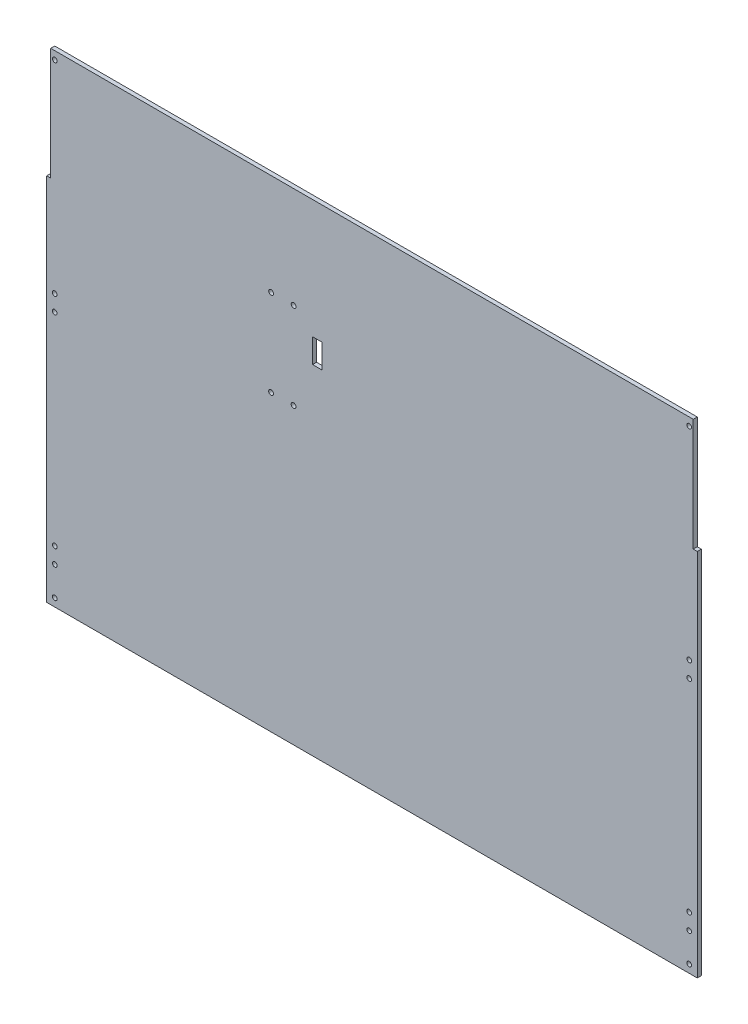
SolidWorks part; units mm, degrees
ref_plane "Front Plane" through (0, 0, 0) normal (0, 0, 1) x (1, 0, 0)
ref_plane "Top Plane" through (0, 0, 0) normal (0, 1, 0) x (1, 0, 0)
ref_plane "Right Plane" through (0, 0, 0) normal (1, 0, 0) x (0, 0, -1)
sketch "Sketch1" plane through (0, 0, 0) normal (0, 0, 1) x (1, 0, 0)
  line L1 (-254, -190.5) -> (254, -190.5)
  line L2 (-254, -190.5) -> (-254, 190.5)
  line L3 (-254, 190.5) -> (254, 190.5)
  line L4 (254, -190.5) -> (254, 190.5)
  line L5 (-254, -190.5) -> (254, 190.5) construction
  line L6 (-254, 190.5) -> (254, -190.5) construction
  point P0 (0, 0)
  dimension "D1" = 508
  dimension "D2" = 381
extrude "Boss-Extrude1" add sketch "Sketch1" along normal blind 3.175
sketch "Sketch3" plane through (0, 0, 3.175) normal (0, 0, 1) x (1, 0, 0)
  line L0 (-254, 190.5) -> (-254, -190.5) construction
  line L1 (-46.99, 77.47) -> (-39.37, 77.47)
  line L2 (-46.99, 77.47) -> (-46.99, 96.52)
  line L3 (-46.99, 96.52) -> (-39.37, 96.52)
  line L4 (-39.37, 77.47) -> (-39.37, 96.52)
  line L5 (254, 190.5) -> (-254, 190.5) construction
  dimension "D1" = 207.01
  dimension "D2" = 7.62
  dimension "D3" = 113.03
  dimension "D4" = 19.05
extrude "Cut-Extrude2" cut sketch "Sketch3" against normal up to surface (3.175 mm away) up to face at (0, 0, 0)
sketch "Sketch2" plane through (0, 0, 3.175) normal (0, 0, 1) x (1, 0, 0)
  line L0 (-250.825, 190.5) -> (-250.825, -190.5) construction
  line L1 (254, 190.5) -> (-254, 190.5) construction
  line L2 (-254, -190.5) -> (254, -190.5) construction
  line L3 (250.825, 190.5) -> (250.825, -190.5) construction
  line L4 (254, -190.5) -> (254, 190.5) construction
  line L5 (-254, 190.5) -> (-254, -190.5) construction
  line L6 (0, 0) -> (0, -50000) construction
  line L8 (-39.37, 96.52) -> (-46.99, 96.52) construction
  circle A0 centre (-250.825, -184.15) radius 1.8542
  circle A1 centre (-250.825, 184.15) radius 1.8542
  circle A2 centre (250.825, 184.15) radius 1.8542
  circle A3 centre (250.825, -184.15) radius 1.8542
  circle A4 centre (-250.825, 24.13) radius 1.8542
  circle A5 centre (250.825, 24.13) radius 1.8542
  circle A6 centre (-250.825, 11.43) radius 1.8542
  circle A7 centre (-250.825, -148.59) radius 1.8542
  circle A8 centre (-250.825, -161.29) radius 1.8542
  circle A9 centre (250.825, -161.29) radius 1.8542
  circle A10 centre (250.825, -148.59) radius 1.8542
  circle A11 centre (250.825, 11.43) radius 1.8542
  circle A12 centre (-79.7747, 110.49) radius 1.905
  circle A13 centre (-79.7747, 41.91) radius 1.905
  circle A14 centre (-61.9947, 110.49) radius 1.905
  circle A15 centre (-61.9947, 41.91) radius 1.905
  point P33 (0, -190.5)
  dimension "D3" = 3.7084
  dimension "D10" = 12.7
  dimension "D14" = 3.81
  dimension "D12" = 17.78
  dimension "D1" = 3.175
  dimension "D2" = 3.175
  dimension "D4" = 6.35
  dimension "D5" = 6.35
  dimension "D6" = 6.35
  dimension "D7" = 6.35
  dimension "D8" = 160.02
  dimension "D9" = 160.02
  dimension "D11" = 29.21
  dimension "D13" = 68.58
  dimension "D15" = 15.0047
  dimension "D16" = 13.97
extrude "Cut-Extrude1" cut sketch "Sketch2" against normal blind 3.175
sketch "Sketch4" plane through (0, 0, 3.175) normal (0, 0, 1) x (1, 0, 0)
  line L0 (254, -190.5) -> (254, 190.5) construction
  line L1 (254, 101.6) -> (257.175, 101.6)
  line L2 (254, 101.6) -> (254, -190.5)
  line L3 (254, -190.5) -> (257.175, -190.5)
  line L4 (257.175, 101.6) -> (257.175, -190.5)
  line L5 (-254, -190.5) -> (254, -190.5) construction
  line L6 (254, 190.5) -> (-254, 190.5) construction
  line L7 (0, 190.5) -> (0, -190.5) construction
  line L8 (-254, -190.5) -> (-257.175, -190.5)
  line L9 (-254, 101.6) -> (-257.175, 101.6)
  line L10 (-254, 101.6) -> (-254, -190.5)
  line L11 (-257.175, 101.6) -> (-257.175, -190.5)
  dimension "D1" = 3.175
  dimension "D2" = 88.9
extrude "Boss-Extrude2" add sketch "Sketch4" against normal blind 3.175
